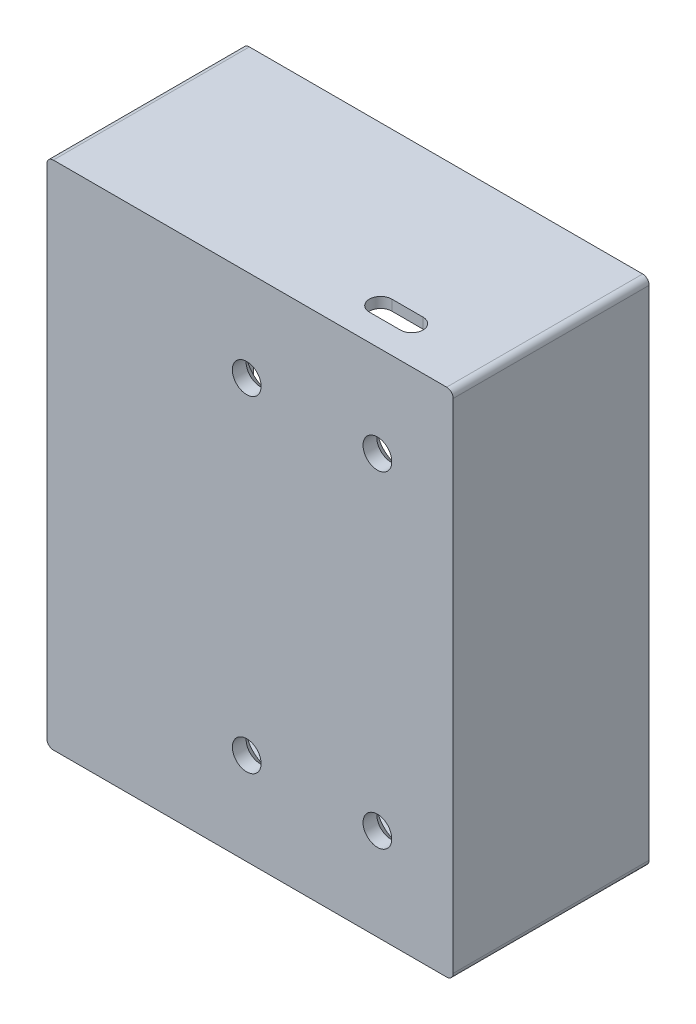
SolidWorks part; units mm, degrees
ref_plane "Спереди" through (0, 0, 0) normal (0, 0, 1) x (1, 0, 0)
ref_plane "Сверху" through (0, 0, 0) normal (0, 1, 0) x (1, 0, 0)
ref_plane "Справа" through (0, 0, 0) normal (1, 0, 0) x (0, 0, -1)
sketch "Эскиз1" plane through (0, 0, 0) normal (0, 0, 1) x (1, 0, 0)
  line L1 (-29.5, -37.5) -> (29.5, -37.5)
  line L2 (-29.5, -37.5) -> (-29.5, 37.5)
  line L3 (-29.5, 37.5) -> (29.5, 37.5)
  line L4 (29.5, -37.5) -> (29.5, 37.5)
  line L5 (-29.5, -37.5) -> (29.5, 37.5) construction
  line L6 (-29.5, 37.5) -> (29.5, -37.5) construction
  point P0 (0, 0)
  dimension "D1" = 59
  dimension "D2" = 75
extrude "Вытянуть-Тонкостенный1" add sketch "Эскиз1" along normal blind 30 thin thin type one direction wall 1.6
sketch "Эскиз2" plane through (0, 0, 30) normal (0, 0, 1) x (1, 0, 0)
  line L1 (-31.1, 39.1) -> (31.1, 39.1)
  line L2 (-31.1, 39.1) -> (-31.1, -39.1)
  line L3 (-31.1, -39.1) -> (31.1, -39.1)
  line L4 (31.1, 39.1) -> (31.1, -39.1)
extrude "Бобышка-Вытянуть1" add sketch "Эскиз2" against normal blind 1.6
sketch "Эскиз3" plane through (0, 0, 28.4) normal (0, 0, -1) x (-1, 0, 0)
  line L1 (-29.5, 37.5) -> (-24.5, 37.5)
  line L2 (-29.5, 37.5) -> (-29.5, 32.5)
  line L3 (-29.5, 32.5) -> (-24.5, 32.5)
  line L4 (-24.5, 37.5) -> (-24.5, 32.5)
  line L5 (29.5, 37.5) -> (24.5, 37.5)
  line L6 (29.5, 37.5) -> (29.5, 32.5)
  line L7 (29.5, 32.5) -> (24.5, 32.5)
  line L8 (24.5, 37.5) -> (24.5, 32.5)
  line L9 (-29.5, -37.5) -> (-24.5, -37.5)
  line L10 (-29.5, -37.5) -> (-29.5, -32.5)
  line L11 (-29.5, -32.5) -> (-24.5, -32.5)
  line L12 (-24.5, -37.5) -> (-24.5, -32.5)
  line L13 (29.5, -37.5) -> (24.5, -37.5)
  line L14 (29.5, -37.5) -> (29.5, -32.5)
  line L15 (29.5, -32.5) -> (24.5, -32.5)
  line L16 (24.5, -37.5) -> (24.5, -32.5)
  dimension "D1" = 5
  dimension "D2" = 5
  dimension "D3" = 5
  dimension "D4" = 5
  dimension "D5" = 5
extrude "Бобышка-Вытянуть2" add sketch "Эскиз3" along normal blind 3
sketch "Эскиз4" plane through (29.5, 0, 0) normal (-1, 0, 0) x (0, 0, 1)
  line L0 (25.4, 37.5) -> (0, 37.5) construction
  line L1 (22.4, 37.5) -> (23.9, 37.5)
  line L2 (22.4, 37.5) -> (22.4, 32.5)
  line L3 (22.4, 32.5) -> (23.9, 32.5)
  line L4 (23.9, 37.5) -> (23.9, 32.5)
  line L5 (25.4, 37.5) -> (25.4, 32.5) construction
  line L6 (25.4, -37.5) -> (0, -37.5) construction
  line L7 (22.4, -37.5) -> (23.9, -37.5)
  line L8 (22.4, -37.5) -> (22.4, -32.5)
  line L9 (22.4, -32.5) -> (23.9, -32.5)
  line L10 (23.9, -37.5) -> (23.9, -32.5)
  line L11 (25.4, -32.5) -> (25.4, -37.5) construction
  dimension "D1" = 1.5
  dimension "D2" = 1.5
  dimension "D3" = 1.5
  dimension "D4" = 1.5
extrude "Бобышка-Вытянуть3" add sketch "Эскиз4" along normal blind 1
sketch "Эскиз5" plane through (-29.5, 0, 0) normal (1, 0, 0) x (0, 0, -1)
  line L0 (-25.4, 37.5) -> (0, 37.5) construction
  line L1 (-22.4, 37.5) -> (-23.9, 37.5)
  line L2 (-22.4, 37.5) -> (-22.4, 32.5)
  line L3 (-22.4, 32.5) -> (-23.9, 32.5)
  line L4 (-23.9, 37.5) -> (-23.9, 32.5)
  line L5 (-25.4, 32.5) -> (-25.4, 37.5) construction
  line L6 (-25.4, -37.5) -> (0, -37.5) construction
  line L7 (-23.9, -37.5) -> (-22.4, -37.5)
  line L8 (-23.9, -37.5) -> (-23.9, -32.7776)
  line L9 (-23.9, -32.7776) -> (-22.4, -32.7776)
  line L10 (-22.4, -37.5) -> (-22.4, -32.7776)
  line L11 (-25.4, -37.5) -> (-25.4, -32.5) construction
  dimension "D1" = 1.5
  dimension "D2" = 1.5
  dimension "D3" = 1.5
  dimension "D4" = 1.5
extrude "Бобышка-Вытянуть4" add sketch "Эскиз5" along normal blind 1
fillet "Скругление1" radius 1 16 edges at (-24.5, -35, 28.4) (-27, -32.5, 28.4) (-27, -32.5, 25.4) (-24.5, -35, 25.4) (27, -32.5, 25.4) (24.5, -35, 25.4) (24.5, -35, 28.4) (27, -32.5, 28.4) (27, 32.5, 28.4) (24.5, 35, 28.4) (27, 32.5, 25.4) (24.5, 35, 25.4) (-24.5, 35, 28.4) (-27, 32.5, 28.4) (-27, 32.5, 25.4) (-24.5, 35, 25.4)
fillet "Скругление2" radius 1.8 4 edges at (29.5, -35, 23.9) (-29.5, -35.1388, 23.9) (-29.5, 35, 23.9) (29.5, 35, 23.9)
sketch "Эскиз6" plane through (0, 0, 28.4) normal (0, 0, -1) x (-1, 0, 0)
  line L0 (-29.5, -31.5) -> (-29.5, 31.5) construction
  line L1 (-19.5, -25) -> (0.5, -25) construction
  line L2 (-19.5, -25) -> (-19.5, 25) construction
  line L3 (-19.5, 25) -> (0.5, 25) construction
  line L4 (0.5, -25) -> (0.5, 25) construction
  line L5 (-19.5, -25) -> (0.5, 25) construction
  line L6 (-19.5, 25) -> (0.5, -25) construction
  circle A0 centre (-19.5, 25) radius 2.2
  circle A1 centre (0.5, 25) radius 2.2
  circle A2 centre (0.5, -25) radius 2.2
  circle A3 centre (-19.5, -25) radius 2.2
  point P0 (-9.5, 0)
  dimension "D1" = 20
  dimension "D2" = 50
  dimension "D3" = 10
extrude "Вырез-Вытянуть1" cut sketch "Эскиз6" against normal through all
sketch "Эскиз7" plane through (0, 0, 28.4) normal (0, 0, -1) x (-1, 0, 0)
  circle A0 centre (-19.5, 25) radius 2.2
  circle A1 centre (-19.5, 25) radius 4
  circle A2 centre (0.5, 25) radius 2.2
  circle A3 centre (0.5, 25) radius 4
  circle A4 centre (-19.5, -25) radius 2.2
  circle A5 centre (-19.5, -25) radius 4
  circle A7 centre (0.5, -25) radius 2.2
  circle A8 centre (0.5, -25) radius 4
extrude "Бобышка-Вытянуть5" add sketch "Эскиз7" along normal blind 2
chamfer "Фаска1" distance 1.5 angle 45 4 edges at (17.3, -25, 26.4) (-2.7, -25, 26.4) (-2.7, 25, 26.4) (17.3, 25, 26.4)
fillet "Скругление3" radius 1 4 edges at (31.1, -39.1, 15) (-31.1, -39.1, 15) (-31.1, 39.1, 15) (31.1, 39.1, 15)
sketch "Эскиз8" plane through (0, 39.1, 0) normal (0, 1, 0) x (1, 0, 0)
  line L0 (18.995, -24.246) -> (14.2398, -24.246) construction
  line L1 (18.995, -25.9685) -> (14.2398, -25.9685)
  line L2 (18.995, -22.5236) -> (14.2398, -22.5236)
  arc A0 (18.995, -25.9685) -> (18.995, -22.5236) centre (18.995, -24.246) ccw
  arc A1 (14.2398, -22.5236) -> (14.2398, -25.9685) centre (14.2398, -24.246) ccw
  point P2 (16.6174, -24.246)
  point P7 (0, 0)
  point P8 (14.2398, -23.7259)
  point P9 (18.0881, -23.7511)
  point P10 (16.6174, -24.246)
extrude "Вырез-Вытянуть2" cut sketch "Эскиз8" against normal up to next
